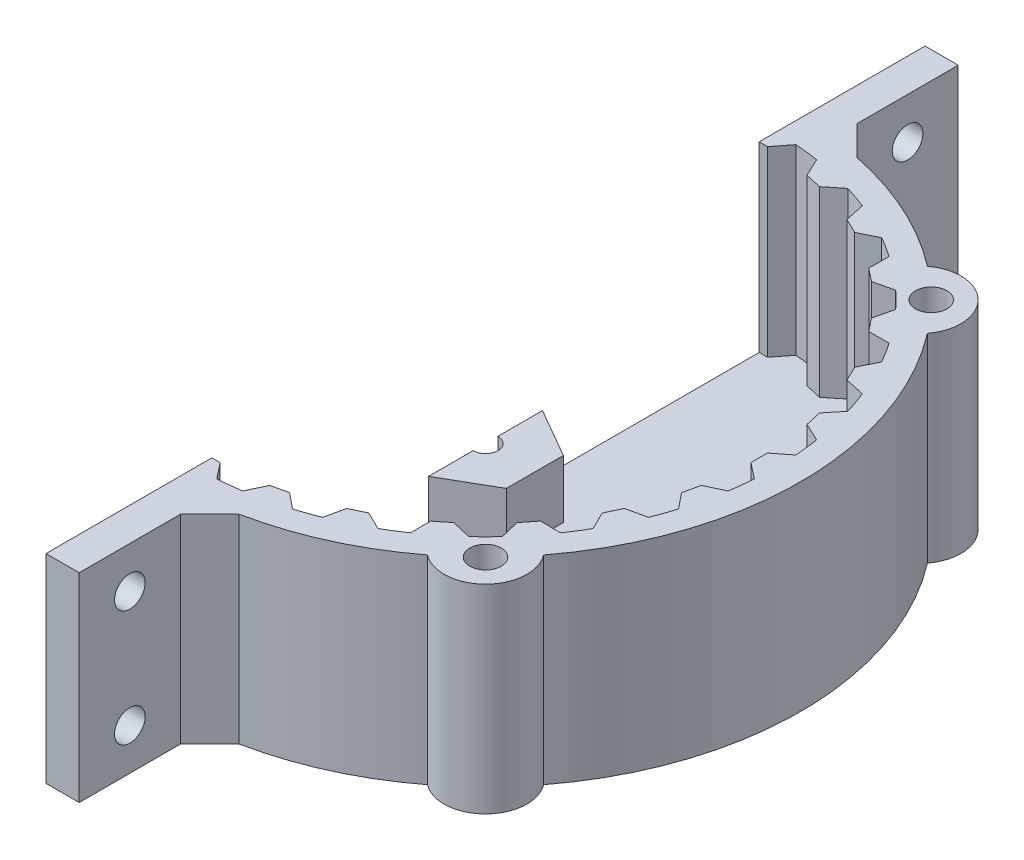
SolidWorks part; units mm, degrees
ref_plane "Front Plane" through (0, 0, 0) normal (0, 0, 1) x (1, 0, 0)
ref_plane "Top Plane" through (0, 0, 0) normal (0, 1, 0) x (1, 0, 0)
ref_plane "Right Plane" through (0, 0, 0) normal (1, 0, 0) x (0, 0, -1)
sketch "Sketch1" plane through (0, 0, 0) normal (0, 1, 0) x (1, 0, 0)
  line L0 (0, 35) -> (0, 33)
  line L1 (0, 33) -> (1, 33)
  line L2 (1, 33) -> (2.5, 34.9106)
  line L3 (0, 33) -> (-1, 33)
  line L4 (-1, 33) -> (-2.5, 34.9106)
  line L5 (0, 0) -> (0, 38) construction
  line L6 (-2.5, 34.9106) -> (2.5, 34.9106) construction
  circle A0 centre (0, 0) radius 35
  circle A1 centre (0, 0) radius 2
  circle A2 centre (0, 0) radius 38
  point P11 (2.5, 34.9106)
  point P13 (1, 33)
  point P14 (-3.6337, 34.9106)
  point P15 (0, 34.9106)
  dimension "D1" = 70
  dimension "D2" = 4
  dimension "D3" = 3
  dimension "D4" = 2.5
  dimension "D6" = 2
  dimension "D7" = 1
extrude "Boss-Extrude6" add sketch "Sketch1" along normal blind 2 contours A1 | L4 A0 L2 L1 L3 A1 | A2 A0 | L0 A0 L4 L3 | L2 A0 L0 L1 region at (0.929, 0, -34.1282) region at (-0.929, 0, -34.1282) region at (0.5, 0, -32.0107) region at (0, 0, 0) region at (-36.9252, 0, 0)
extrude "Boss-Extrude7" add sketch "Sketch1<7>" along normal blind 24 contours A2 A0 region at (-36.9252, 0, 0)
sketch "Sketch1<7>" plane through (0, 0, 0) normal (0, 1, 0) x (1, 0, 0) same geometry as "Sketch1"
extrude "Boss-Extrude8" add sketch "Sketch1<8>" along normal up to surface (24 mm away) contours L2 A0 L0 L1 | L0 A0 L4 L3 region at (0.929, 0, -34.1282) region at (-0.929, 0, -34.1282) up to face at (0, 24, 35)
sketch "Sketch1<8>" plane through (0, 0, 0) normal (0, 1, 0) x (1, 0, 0) same geometry as "Sketch1"
pattern_circular "CirPattern1" count 28 over 360 about axis through (0, 24, 0) along (0, -1, 0) of "Boss-Extrude8"
sketch "Sketch3" plane through (0, 0, 0) normal (0, 1, 0) x (1, 0, 0)
  line L2 (0, -38) -> (0, -53)
  line L3 (0, -53) -> (4, -53)
  line L4 (4, -40.7809) -> (4, -53)
  line L5 (0, 0) -> (0, -38) construction
  line L6 (4, -40.7809) -> (7.5355, -37.2453)
  circle A0 centre (0, 0) radius 38 construction
  arc A1 (0, -38) -> (7.5355, -37.2453) centre (0, 0) ccw
  point P4 (4, -41.3282)
  dimension "D1" = 4
  dimension "D2" = 15
  dimension "D3" = 5
  dimension "D4" = 45
extrude "Boss-Extrude9" add sketch "Sketch3" along normal up to surface (24 mm away) up to face at (0, 24, 0)
sketch "Sketch4" plane through (0, 0, 0) normal (1, 0, 0) x (0, 0, -1)
  line L0 (-46.8904, 5) -> (-46.8904, 19) construction
  line L1 (-53, 12) -> (0, 12) construction
  line L2 (-53, 24) -> (-53, 0) construction
  line L3 (0, 24) -> (0, 0) construction
  line L5 (-46.8904, 0) -> (-46.8904, 24) construction
  line L6 (-53, 0) -> (-40.7809, 0) construction
  line L7 (-53, 24) -> (-40.7809, 24) construction
  circle A0 centre (-46.8904, 5) radius 1.85
  circle A1 centre (-46.8904, 19) radius 1.85
  point P6 (-46.8904, 12)
  point P7 (-46.8904, 19.5)
  dimension "D1" = 3.7
  dimension "D2" = 14
extrude "Cut-Extrude2" cut sketch "Sketch4" along normal up to surface (4 mm away) up to face at (4, 12, 46.8904)
mirror "Mirror1" about plane through (0, 0, 0) normal (0, 0, 1) of "Cut-Extrude2", "Boss-Extrude9"
sketch "Sketch6" plane through (0, 0, 0) normal (0, 1, 0) x (1, 0, 0)
  line L1 (0, 6.8705) -> (-5.95, 3.4352)
  line L2 (-5.95, 3.4352) -> (-5.95, -3.4352)
  line L3 (-5.95, -3.4352) -> (0, -6.8705)
  line L4 (0, -6.8705) -> (5.95, -3.4352)
  line L5 (5.95, -3.4352) -> (5.95, 3.4352)
  line L6 (5.95, 3.4352) -> (0, 6.8705)
  circle A0 centre (0, 0) radius 5.95 construction
  dimension "D1" = 11.9
extrude "Boss-Extrude12" add sketch "Sketch6" along a picked direction on the side of the normal blind 9
sketch "Sketch7" plane through (0, 0, 0) normal (0, 1, 0) x (1, 0, 0)
  circle A0 centre (0, 0) radius 1.5
  dimension "D1" = 3
extrude "Cut-Extrude4" cut sketch "Sketch7" along normal up to surface (9 mm away) up to face at (0, 9, 0)
sketch "Sketch11" plane through (0, 0, 0) normal (0, 1, 0) x (1, 0, 0)
  line L0 (0, 0) -> (26.8701, 26.8701) construction
  line L5 (26.8701, 26.8701) -> (29.6985, 29.6985) construction
  circle A1 centre (26.8701, 26.8701) radius 1.9
  arc A4 (25.4934, 28.1796) -> (28.1796, 25.4934) centre (0, 0) ccw construction
  arc A5 (30.1438, 23.1376) -> (28.1796, 25.4934) centre (0, 0) ccw
  arc A6 (25.4934, 28.1796) -> (23.1376, 30.1438) centre (0, 0) ccw
  arc A7 (30.1438, 23.1376) -> (23.1376, 30.1438) centre (26.163, 26.163) ccw
  dimension "D2" = 3.8
  dimension "D1" = 5
  dimension "D3" = 4
extrude "Boss-Extrude17" add sketch "Sketch11" along normal up to surface (24 mm away) contours A5 A7 A6 A1 region at (27.6173, 0, -28.7398) up to face at (0, 24, 0)
extrude "Cut-Extrude7" cut sketch "Sketch11<10>" along normal up to surface (24 mm away) contours A1 region at (26.8701, 0, -26.8701) up to face at (5.547, 24, -4.2467)
sketch "Sketch11<10>" plane through (0, 0, 0) normal (0, 1, 0) x (1, 0, 0) same geometry as "Sketch11"
pattern_circular "CirPattern2" count 4 over 360 about axis through (0, 2, 0) along (0, -1, 0) of "Boss-Extrude17", "Cut-Extrude7"
sketch "Sketch5" plane through (0, 0, 0) normal (0, 1, 0) x (1, 0, 0)
  line L1 (0, 55.9861) -> (-41.0866, 55.9861)
  line L2 (0, 55.9861) -> (0, -59.8239)
  line L3 (0, -59.8239) -> (-41.0866, -59.8239)
  line L4 (-41.0866, 55.9861) -> (-41.0866, -59.8239)
extrude "Cut-Extrude3" cut sketch "Sketch5" along normal up to surface (24 mm away) up to face at (1.6992, 24, 0)
